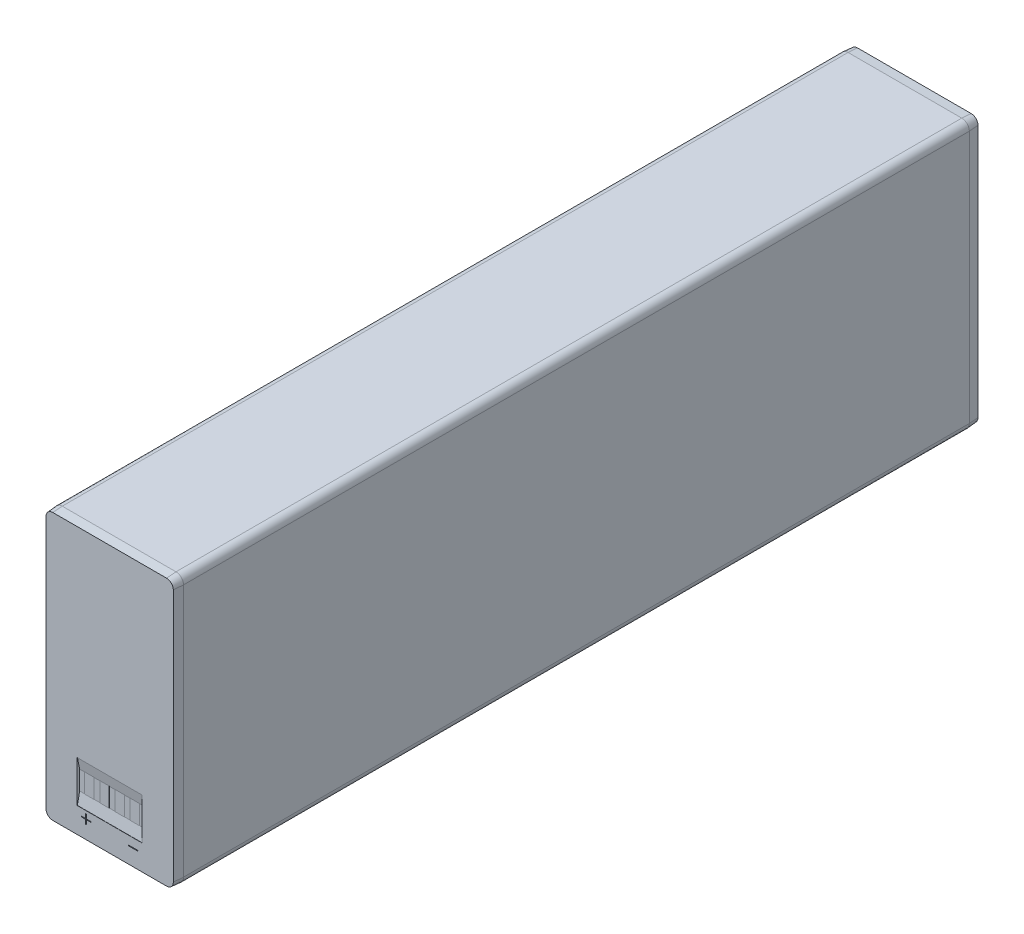
SolidWorks part; units mm, degrees
ref_plane "Face" through (0, 0, 0) normal (0, 0, 1) x (1, 0, 0)
ref_plane "Dessus" through (0, 0, 0) normal (0, 1, 0) x (1, 0, 0)
ref_plane "Droite" through (0, 0, 0) normal (1, 0, 0) x (0, 0, -1)
sketch "Esquisse1" plane through (0, 0, 0) normal (0, 0, 1) x (1, 0, 0)
  line L0 (-17.05, 35.5) -> (17.05, -35.5) construction
  line L1 (-17.05, -35.5) -> (17.05, -35.5)
  line L2 (-17.05, -35.5) -> (-17.05, 35.5)
  line L3 (-17.05, 35.5) -> (17.05, 35.5)
  line L4 (17.05, -35.5) -> (17.05, 35.5)
  line L5 (17.05, 35.5) -> (-17.05, -35.5) construction
  point P4 (0, 0)
  dimension "D1" = 71
  dimension "D2" = 34.1
extrude "Extrusion1" add sketch "Esquisse1" along normal blind 213
sketch "Esquisse2" plane through (0, 0, 213) normal (0, 0, 1) x (1, 0, 0)
  line L0 (0, -35.5) -> (0, 65.4329) construction
  line L1 (-7.3, -20.15) -> (7.3, -20.15)
  line L2 (-7.3, -20.15) -> (-7.3, -26.15)
  line L3 (-7.3, -26.15) -> (7.3, -26.15)
  line L4 (7.3, -20.15) -> (7.3, -26.15)
  line L5 (-17.05, -35.5) -> (17.05, -35.5) construction
  dimension "D1" = 7.3
  dimension "D2" = 7.3
  dimension "D3" = 9.35
  dimension "D4" = 6
extrude "Enlèv. mat.-Extru.1" cut sketch "Esquisse2" against normal blind 0.65
sketch "Sketch1" plane through (0, 0, 213) normal (0, 0, 1) x (1, 0, 0)
  line L0 (-6.25, -29.35) -> (-6.25, 4.0105) construction
  line L1 (-6.35, -29.35) -> (-6.15, -29.35)
  line L2 (-6.35, -29.35) -> (-6.35, -30.5)
  line L3 (-6.35, -31.85) -> (-6.15, -31.85)
  line L4 (-6.15, -29.35) -> (-6.15, -30.5)
  line L5 (-7.5, -30.5) -> (-6.35, -30.5)
  line L6 (-7.5, -30.5) -> (-7.5, -30.7)
  line L7 (-7.5, -30.7) -> (-6.35, -30.7)
  line L8 (-5, -30.5) -> (-5, -30.7)
  line L9 (8.8215, -30.6) -> (-7.5, -30.6) construction
  line L10 (0, -26.15) -> (0, -2.5478) construction
  line L12 (-7.5, -30.6) -> (26.1207, -30.6) construction
  line L13 (5, -30.9) -> (7.5, -30.9)
  line L14 (5, -30.9) -> (5, -31.1)
  line L15 (5, -31.1) -> (7.5, -31.1)
  line L16 (7.5, -30.9) -> (7.5, -31.1)
  line L17 (-6.15, -30.5) -> (-5, -30.5)
  line L18 (-6.35, -30.7) -> (-6.35, -31.85)
  line L19 (-6.15, -30.7) -> (-5, -30.7)
  line L20 (-6.15, -30.7) -> (-6.15, -31.85)
  line L21 (-7.3, -26.15) -> (7.3, -26.15) construction
  dimension "D1" = 0.2
  dimension "D2" = 10
  dimension "D3" = 2.5
  dimension "D5" = 2.5
  dimension "D7" = 3.2
  dimension "D9" = 2.5
  dimension "D10" = 0.2
  dimension "D11" = 0.5
extrude "Cut-Extrude1" cut sketch "Sketch1" against normal blind 1
sketch "Sketch2" plane through (0, 0, 213) normal (0, 0, 1) x (1, 0, 0)
  line L0 (0, -35.5) -> (0, 36.8927) construction
  line L1 (-8.6, -17.65) -> (8.6, -17.65)
  line L2 (-8.6, -17.65) -> (-8.6, -28.65)
  line L3 (-8.6, -28.65) -> (8.6, -28.65)
  line L4 (8.6, -17.65) -> (8.6, -28.65)
  line L5 (-17.05, -35.5) -> (17.05, -35.5) construction
  line L6 (-7.3, -23.15) -> (7.3, -23.15) construction
  line L7 (-7.3, -20.15) -> (-7.3, -26.15) construction
  line L8 (7.3, -26.15) -> (7.3, -20.15) construction
  line L9 (-7.3, -26.15) -> (7.3, -26.15) construction
  line L10 (-7.3, -20.15) -> (-4.8, -20.15)
  line L11 (-7.3, -20.15) -> (-7.3, -26.15)
  line L12 (-7.3, -26.15) -> (-4.8, -26.15)
  line L13 (-4.8, -20.15) -> (-4.8, -26.15)
  line L14 (-3.2667, -20.15) -> (-0.7667, -20.15)
  line L15 (-3.2667, -20.15) -> (-3.2667, -26.15)
  line L16 (-3.2667, -26.15) -> (-0.7667, -26.15)
  line L17 (-0.7667, -20.15) -> (-0.7667, -26.15)
  line L18 (0.7667, -20.15) -> (3.2667, -20.15)
  line L19 (0.7667, -20.15) -> (0.7667, -26.15)
  line L20 (0.7667, -26.15) -> (3.2667, -26.15)
  line L21 (3.2667, -20.15) -> (3.2667, -26.15)
  line L22 (4.8, -20.15) -> (7.3, -20.15)
  line L23 (4.8, -20.15) -> (4.8, -26.15)
  line L24 (4.8, -26.15) -> (7.3, -26.15)
  line L25 (7.3, -20.15) -> (7.3, -26.15)
  line M17 (7.3, -26.15) -> (-7.3, -26.15)
  line M18 (-7.3, -26.15) -> (-7.3, -20.15)
  line M19 (-7.3, -20.15) -> (7.3, -20.15)
  line M20 (7.3, -20.15) -> (7.3, -26.15)
  dimension "D1" = 11
  dimension "D2" = 17.2
  dimension "D3" = 2.5
  dimension "D4" = 4
extrude "Cut-Extrude2" cut sketch "Sketch2" against normal blind 0.66 contours L4 L1 L2 L3 M20 M17 M18 M19 | L15 L13 M19 M17 | L19 L17 M19 M17 | L23 L21 M19 M17 region at (0, -17.8542, 213) region at (-4.0333, -23.15, 213) region at (0, -23.15, 213) region at (4.0333, -23.15, 213)
chamfer "Chamfer1" distance 3 distance2 0.6 2 edges at (0, -17.65, 212.34) (0, -28.65, 212.34) first distance on face at (2.0167, -23.15, 212.34)
fillet "Fillet1" radius 2 4 edges at (-17.05, -35.5, 106.5) (17.05, -35.5, 106.5) (17.05, 35.5, 106.5) (-17.05, 35.5, 106.5)
chamfer "Chamfer2" distance 2.5 distance2 0.2 8 edges at (-17.05, 0, 213) (-16.4642, -34.9142, 213) (0, -35.5, 213) (16.4642, -34.9142, 213) (17.05, 0, 213) (16.4642, 34.9142, 213) (0, 35.5, 213) (-16.4642, 34.9142, 213) first distance on face at (-17.05, 0, 106.5) first distance on face at (-16.2571, -34.7071, 106.5) first distance on face at (0, -35.5, 106.5) first distance on face at (16.2571, -34.7071, 106.5) first distance on face at (17.05, 0, 106.5) first distance on face at (16.2571, 34.7071, 106.5) first distance on face at (0, 35.5, 106.5) first distance on face at (-16.2571, 34.7071, 106.5)
chamfer "Chamfer3" distance 2.5 distance2 0.2 8 edges at (-17.05, 0, 0) (-16.4642, -34.9142, 0) (0, -35.5, 0) (16.4642, -34.9142, 0) (17.05, 0, 0) (16.4642, 34.9142, 0) (0, 35.5, 0) (-16.4642, 34.9142, 0) first distance on face at (-17.05, 0, 105.25) first distance on face at (-16.2571, -34.7071, 105.25) first distance on face at (0, -35.5, 105.25) first distance on face at (16.2571, -34.7071, 105.25) first distance on face at (17.05, 0, 105.25) first distance on face at (16.2571, 34.7071, 105.25) first distance on face at (0, 35.5, 105.25) first distance on face at (-16.2571, 34.7071, 105.25)
